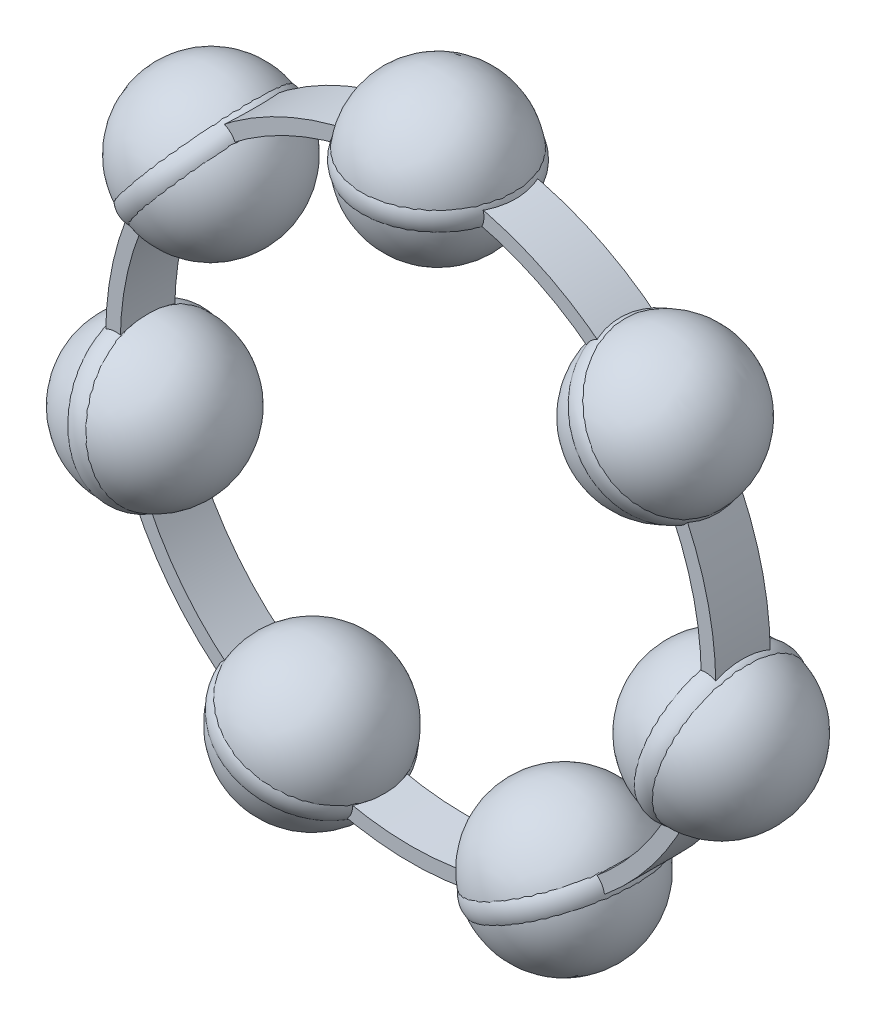
SolidWorks part; units mm, degrees
ref_plane "Front Plane" through (0, 0, 0) normal (0, 0, 1) x (1, 0, 0)
ref_plane "Top Plane" through (0, 0, 0) normal (0, 1, 0) x (1, 0, 0)
ref_plane "Right Plane" through (0, 0, 0) normal (1, 0, 0) x (0, 0, -1)
sketch "Sketch1" plane through (0, 0, 0) normal (0, 0, 1) x (1, 0, 0)
  line L0 (-7.9375, 0) -> (7.9375, 0) construction
  line L1 (-4.7625, 0) -> (4.7625, 0) construction
  circle A0 centre (0, 0) radius 4.7625 construction
  circle A1 centre (0, 0) radius 7.9375 construction
  point P3 (0, 0)
  point P6 (0, 0)
  point P7 (0, -4.7625)
  point P11 (0, -7.9375)
  point P12 (0, 4.7625)
  point P13 (0, 7.9375)
  dimension "OD" = 15.875
  dimension "ID" = 9.525
sketch "SketchB" plane through (0, 0, 0) normal (1, 0, 0) x (0, 0, -1)
  line L0 (-3.5719, 7.9375) -> (3.5719, 7.9375) construction
  line L1 (0, 7.9375) -> (0, -7.9375) construction
  line L2 (3.2147, 7.9375) -> (-3.2147, 7.9375)
  line L3 (-3.2147, 7.9375) -> (-3.5719, 7.5803)
  line L4 (-3.5719, 7.5803) -> (-3.5719, 6.8873)
  line L5 (-3.5719, 6.8873) -> (-1.5875, 6.8873)
  line L6 (3.5719, 6.8873) -> (1.5875, 6.8873)
  line L7 (3.5719, 7.5803) -> (3.5719, 6.8873)
  line L8 (3.2147, 7.9375) -> (3.5719, 7.5803)
  line L9 (0, 7.9375) -> (0, 6.35) construction
  line L10 (0, 6.35) -> (0, 4.7625) construction
  line L11 (0, 7.9375) -> (0, -7.9375) construction
  line L12 (-3.5719, 0) -> (3.5719, 0) construction
  line L13 (3.5719, 4.7625) -> (-3.5719, 4.7625) construction
  line L14 (0, 8.026) -> (0, 4.674) construction
  line L15 (-3.5719, -4.7625) -> (3.5719, -4.7625) construction
  arc A0 (-1.5875, 6.8873) -> (1.5875, 6.8873) centre (0, 6.35) cw
  circle A1 centre (0, 6.35) radius 1.676 construction
  point P14 (0, 4.7625)
  point P17 (0, 0)
  point P21 (0, 7.9375)
  point P29 (0, 4.7625)
  point P30 (0, -4.7625)
  point P35 (0, 8.026)
  dimension "Width" = 7.1437
  dimension "D1" = 45
  dimension "D2" = 0.3572
  dimension "D3" = 3.175
  dimension "D4" = 0.5373
sketch "Sketch7" plane through (0, 0, 0) normal (1, 0, 0) x (0, 0, -1)
  line L0 (3.2147, 7.9375) -> (3.5719, 7.5803) construction
  line L1 (3.5719, 7.5803) -> (3.5719, 6.8873) construction
  line L2 (3.5719, 6.8873) -> (1.5875, 6.8873) construction
  line L3 (-3.5719, 6.8873) -> (-1.5875, 6.8873) construction
  line L4 (-3.5719, 7.5803) -> (-3.5719, 6.8873) construction
  line L5 (-3.2147, 7.9375) -> (-3.5719, 7.5803) construction
  line L6 (3.2147, 7.9375) -> (-3.2147, 7.9375) construction
  line L7 (3.2147, 7.9375) -> (3.5719, 7.5803)
  line L8 (3.5719, 7.5803) -> (3.5719, 6.8873)
  line L9 (3.5719, 6.8873) -> (1.5875, 6.8873)
  line L10 (-3.5719, 6.8873) -> (-1.5875, 6.8873)
  line L11 (-3.5719, 7.5803) -> (-3.5719, 6.8873)
  line L12 (-3.2147, 7.9375) -> (-3.5719, 7.5803)
  line L13 (3.2147, 7.9375) -> (-3.2147, 7.9375)
  arc A0 (1.5875, 6.8873) -> (-1.5875, 6.8873) centre (0, 6.35) ccw construction
  arc A1 (1.5875, 6.8873) -> (-1.5875, 6.8873) centre (0, 6.35) ccw
revolve "Revolve6" add sketch "Sketch7" angle 360 about L12 rebuild error yes
sketch "Sketch3" plane through (0, 0, 0) normal (1, 0, 0) x (0, 0, -1)
  line L0 (0, 7.9375) -> (0, -7.9375) construction
  line L1 (0, 7.9375) -> (0, -7.9375) construction
  line L2 (-2.5003, 4.7625) -> (-2.7781, 5.1844)
  line L3 (-2.7781, 5.1844) -> (-2.7781, 5.8774)
  line L5 (-2.7781, 5.8774) -> (-1.6079, 5.8774)
  line L6 (-2.5003, 4.7625) -> (2.5003, 4.7625)
  line L8 (2.5003, 4.7625) -> (2.7781, 5.1844)
  line L10 (2.7781, 5.1844) -> (2.7781, 5.8774)
  line L11 (2.7781, 5.8774) -> (1.6079, 5.8774)
  line L12 (-3.5719, 7.5803) -> (-3.5719, 6.8873) construction
  line L13 (3.2147, 7.9375) -> (3.5719, 7.5803) construction
  line L15 (2.7781, -7.6597) -> (2.7781, 7.6597) construction
  line L16 (2.5003, 7.9375) -> (2.5003, -7.9375) construction
  arc A1 (1.6079, 5.8774) -> (-1.6079, 5.8774) centre (0, 6.35) cw
  circle A2 centre (0, 6.35) radius 1.676 construction
  point P1 (0, 4.7625)
revolve "Revolve3" add sketch "Sketch3" angle 360 about L12 rebuild error yes
sketch "Sketch4" plane through (0, 0, 0) normal (1, 0, 0) x (0, 0, -1)
  line L0 (-1.676, 6.35) -> (1.676, 6.35)
  arc A2 (-1.676, 6.35) -> (1.676, 6.35) centre (0, 6.35) cw
  arc A3 (1.5875, 6.8873) -> (-1.5875, 6.8873) centre (0, 6.35) ccw construction
revolve "Revolve4" add sketch "Sketch4" angle 360 about L0
sketch "Sketch8" plane through (0, 0, 0) normal (1, 0, 0) x (0, 0, -1)
  line L0 (-1.5875, 6.8873) -> (-1.5875, 6.6675) construction
  line L1 (-1.5875, 6.6675) -> (-1.5875, 6.4477) construction
  line L2 (-1.5875, 6.4477) -> (-1.5875, 6.2279) construction
  line L3 (-1.5875, 6.2279) -> (-1.5875, 6.0081) construction
  line L4 (-2.7781, 6.6675) -> (-2.5404, 6.6675) construction
  line L5 (-1.5875, 6.6675) -> (-1.5875, 6.2279) construction
  line L7 (-2.5404, 6.6675) -> (-2.3026, 6.6675) construction
  line L8 (-2.3026, 6.6675) -> (-2.0649, 6.6675) construction
  line L10 (0, 7.9375) -> (0, -7.9375) construction
  line L11 (0, 7.9375) -> (0, -7.9375) construction
  line L12 (-2.7781, 6.985) -> (-2.7781, 6.6675) construction
  line L13 (-1.5894, 6.6675) -> (-1.3516, 6.6675) construction
  line L14 (-2.7781, 7.6597) -> (-2.7781, -7.6597) construction
  line L15 (-2.7781, 6.6675) -> (-2.7781, 6.35) construction
  line L16 (-2.7781, 6.35) -> (-2.7781, 6.0325) construction
  line L17 (-2.7781, 6.0325) -> (-2.7781, 5.715) construction
  line L18 (-2.0649, 6.6675) -> (-1.8271, 6.6675) construction
  line L19 (-1.8271, 6.6675) -> (-1.5894, 6.6675) construction
  line L20 (-1.3516, 6.6675) -> (-1.5894, 6.6675)
  line L21 (-2.7781, 6.0325) -> (-2.5404, 6.0325) construction
  line L22 (-2.5404, 6.0325) -> (-2.3026, 6.0325) construction
  line L23 (-2.3026, 6.0325) -> (-2.0649, 6.0325) construction
  line L24 (-2.0649, 6.0325) -> (-1.8271, 6.0325) construction
  line L25 (-1.8271, 6.0325) -> (-1.5894, 6.0325) construction
  line L26 (-1.5894, 6.0325) -> (-1.3516, 6.0325) construction
  line L27 (-1.3516, 6.0325) -> (-1.5894, 6.0325)
  line L28 (-1.8271, 6.6675) -> (-1.8271, 6.0325) construction
  line L30 (-1.7083, 6.6675) -> (-1.7083, 6.0325) construction
  circle A0 centre (0, 6.35) radius 1.676 construction
  arc A2 (-1.5894, 6.0325) -> (-1.5894, 6.6675) centre (-1.2248, 6.35) cw
  arc A3 (-1.3516, 6.6675) -> (-1.3516, 6.0325) centre (0, 6.35) ccw
revolve "Revolve7" add sketch "Sketch8" angle 360 about L11
pattern_circular "CirPattern1" count 7 over 360 about axis through (0, 0, 3.5719) along (0, 0, -1) of bodies 134 104
sketch "Sketch9" plane through (0, 0, 0) normal (0, 0, 1) x (1, 0, 0)
  line L0 (0, 5.715) -> (0, 5.9267) construction
  line L1 (0, 4.674) -> (0, 8.026) construction
  line L2 (0, 5.9267) -> (0, 6.1383) construction
  line L3 (0, 6.1383) -> (0, 6.35) construction
  line L4 (0, 6.35) -> (0, 6.5617) construction
  line L5 (0, 6.5617) -> (0, 6.7733) construction
  line L6 (0, 6.7733) -> (0, 6.985) construction
  line L7 (0, 7.5803) -> (0, 6.8873) construction
  line L8 (0, 7.9375) -> (0, -7.9375) construction
  circle A0 centre (0, 0) radius 5.715 construction
  circle A1 centre (0, 0) radius 6.35
  circle A2 centre (0, 0) radius 6.6675
  point P19 (0, 6.6675)
extrude "Boss-Extrude1" add sketch "Sketch9" along normal mid plane 1.1906 separate body
equation "\"D2@SketchB\" = \"Width@SketchB\" * .05"
equation "\"D3@SketchB\" = \"Width@SketchB\" / 2.25"
equation "\"D4@SketchB\" =  (  (  ( \"OD@Sketch1\" - \"Width@SketchB\" )  / 2 )  / 3.25 )  / 2.5"
equation "\"D1@Boss-Extrude1\"=\"Width@SketchB\"/6"
